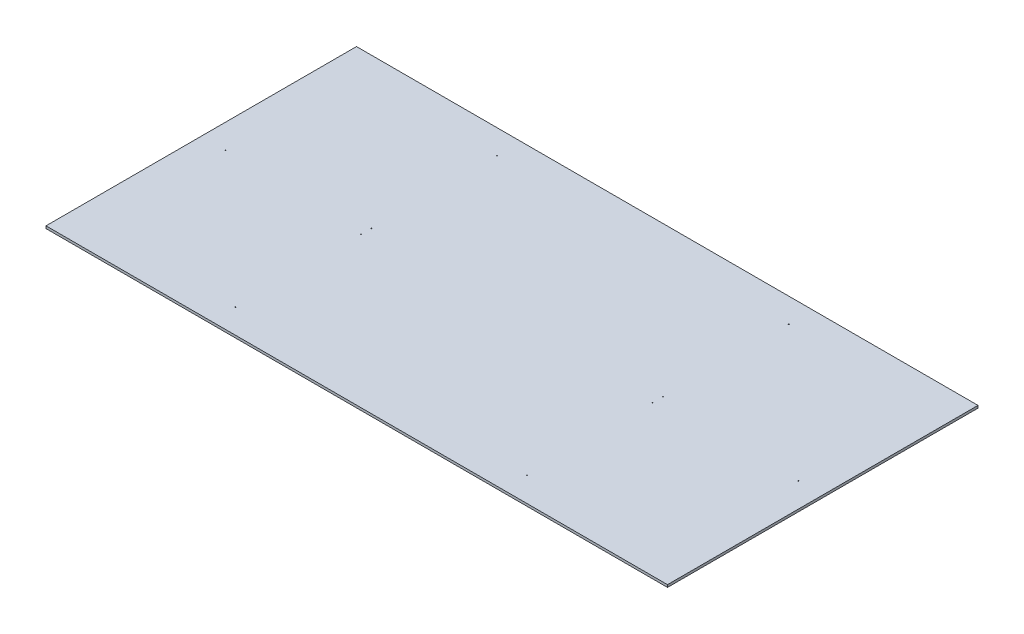
SolidWorks part; units mm, degrees
ref_plane "Front Plane" through (0, 0, 0) normal (0, 0, 1) x (1, 0, 0)
ref_plane "Top Plane" through (0, 0, 0) normal (0, 1, 0) x (1, 0, 0)
ref_plane "Right Plane" through (0, 0, 0) normal (1, 0, 0) x (0, 0, -1)
sketch "Sketch1" plane through (0, 0, 0) normal (0, 1, 0) x (1, 0, 0)
  line L1 (-127.9, -63.9) -> (127.9, -63.9)
  line L2 (-127.9, -63.9) -> (-127.9, 63.9)
  line L3 (-127.9, 63.9) -> (127.9, 63.9)
  line L4 (127.9, -63.9) -> (127.9, 63.9)
  line L5 (-127.9, -63.9) -> (127.9, 63.9) construction
  line L6 (-127.9, 63.9) -> (127.9, -63.9) construction
  point P0 (0, 0)
  dimension "D1" = 127.8
  dimension "D2" = 255.8
extrude "Boss-Extrude1" add sketch "Sketch1" along normal blind 1 contours L2 L1 L4 L3
sketch "Sketch2" plane through (0, 1, 0) normal (0, 1, 0) x (1, 0, 0)
  line L0 (-127.9, -63.9) -> (-127.9, 63.9) construction
  line L1 (-127.9, -63.9) -> (127.9, -63.9) construction
  line L2 (-127.9, 0) -> (127.9, 0)
  line L4 (-127.9, 63.9) -> (127.9, 63.9) construction
  line L5 (127.9, -63.9) -> (127.9, 63.9) construction
  line L6 (0, 63.9) -> (0, -63.9)
  point P0 (-117.875, 0)
  point P10 (-60, 2.125)
  point P11 (-60, 53.875)
  point P15 (-60, -2.125)
  point P16 (-60, -53.875)
  point P17 (117.875, 0)
  point P18 (60, -53.875)
  point P19 (60, -2.125)
  point P20 (60, 2.125)
  point P21 (60, 53.875)
  dimension "D1" = 10.025
  dimension "D2" = 63.9
  dimension "D3" = 67.9
  dimension "D4" = 2.125
  dimension "D5" = 10.025
  dimension "D6" = 67.9
hole_wizard "Ø0.35 (0.35) Diameter Hole1" positions "Sketch2" profile "Sketch3" hole size "Ø0.35" standard "ANSI Metric" end condition through all
sketch "Sketch3" plane through (-117.875, 1, 0) normal (1, 0, 0) x (0, 0, 1)
  line L0 (0, 0) -> (0, 1)
  line L1 (0, 1) -> (0.175, 1)
  line L2 (0.175, 1) -> (0.175, 0)
  line L5 (0.175, 0) -> (0, 0)
  line L11 (0, -6.35) -> (0, 107.95) construction
  dimension "Thru Hole Dia." = 0.35
  dimension "Thru Hole Depth" = 1
equation "\"H\"=63.9"
